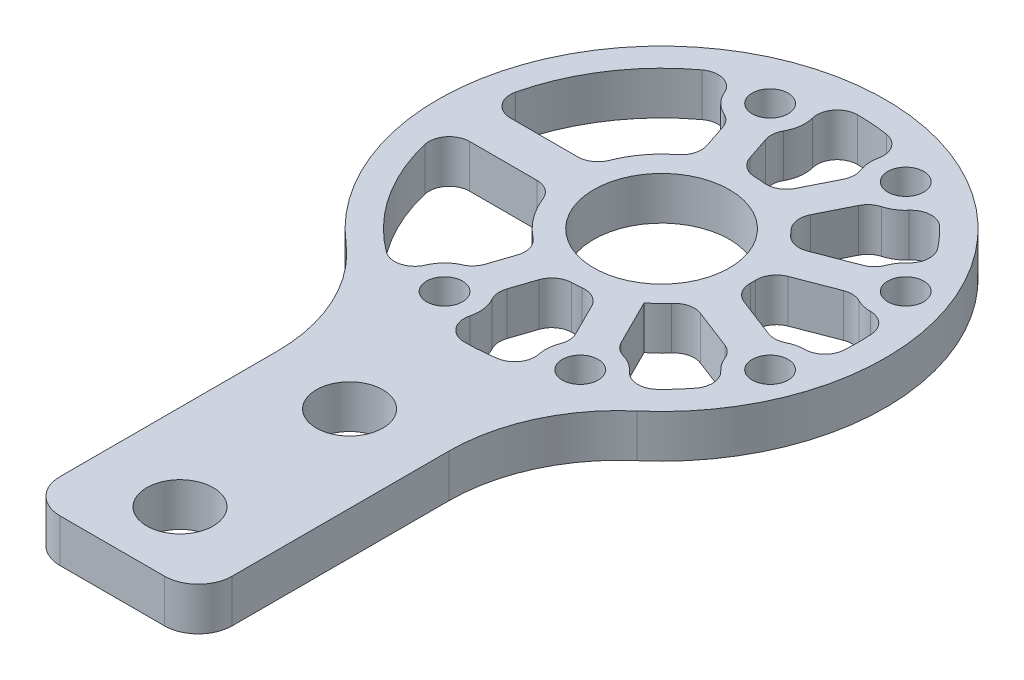
SolidWorks part; units mm, degrees
material "1060 Alloy"
ref_plane "Front Plane" through (0, 0, 0) normal (0, 0, 1) x (1, 0, 0)
ref_plane "Top Plane" through (0, 0, 0) normal (0, 1, 0) x (1, 0, 0)
ref_plane "Right Plane" through (0, 0, 0) normal (1, 0, 0) x (0, 0, -1)
sketch "Sketch1" plane through (0, 0, 0) normal (0, 1, 0) x (1, 0, 0)
  line L0 (-12.7, -81) -> (12.7, -81)
  line L1 (12.7, -81) -> (12.7, -30.4583)
  line L2 (-12.7, -81) -> (-12.7, -30.4583)
  line L3 (0, -81) -> (0, -46) construction
  arc A0 (12.7, -30.4583) -> (-12.7, -30.4583) centre (0, 0) ccw
  point P5 (0, -81)
  point P9 (0, -71)
  dimension "D2" = 66
  dimension "D1" = 25.4
  dimension "D3" = 46
  dimension "D4" = 25
  dimension "D5" = 10
extrude "Boss-Extrude1" add sketch "Sketch1" along normal blind 6.35 contours A0 L2 L0 L1
sketch "Sketch2" plane through (0, 0, 0) normal (0, -1, 0) x (1, 0, 0)
  point P14 (12, -24)
  point P16 (-8, -24)
  point P19 (2, 0)
  point P21 (26, 10)
  point P22 (26, -10)
  point P23 (-22, -10)
  point P24 (-22, 10)
  point P25 (-8, 24)
  point P26 (12, 24)
  point P27 (2, 0)
  dimension "D2" = 10
  dimension "D1" = 20
  dimension "D3" = 2
  dimension "D4" = 24
  dimension "D5" = 4
sketch "Sketch5" plane through (0, 0, 0) normal (0, -1, 0) x (1, 0, 0)
  circle A0 centre (0, 0) radius 10
  dimension "D1" = 20
extrude "Cut-Extrude1" cut sketch "Sketch5" against normal through all
hole_wizard "3/8 Clearance Hole1" positions "Sketch13" profile "Sketch14" hole size "3/8" standard "ANSI Inch" end condition through all
sketch "Sketch13" plane through (0, 0, 0) normal (0, -1, 0) x (-1, 0, 0)
  point P0 (0, -46)
  point P3 (0, -71)
sketch "Sketch14" plane through (0, 0, 46) normal (1, 0, 0) x (0, 0, -1)
  line L0 (0, 0) -> (0, 6.35)
  line L1 (0, 6.35) -> (4.9022, 6.35)
  line L2 (4.9022, 6.35) -> (4.9022, 0)
  line L5 (4.9022, 0) -> (0, 0)
  line L11 (0, -6.35) -> (0, 107.95) construction
  dimension "Thru Hole Dia." = 9.8044
  dimension "Thru Hole Depth" = 6.35
fillet "Fillet1" radius 25 2 edges at (-12.7, 3.175, 30.4583) (12.7, 3.175, 30.4583)
hole_wizard "M5 Clearance Hole1" positions "Sketch18" profile "Sketch19" hole size "M5" standard "ANSI Metric" end condition through all
sketch "Sketch18" plane through (0, 0, 0) normal (0, -1, 0) x (-1, 0, 0)
  point P0 (8, 24)
  point P3 (-12, 24)
  point P6 (-26, 10)
  point P9 (-26, -10)
  point P12 (-12, -24)
  point P15 (8, -24)
sketch "Sketch19" plane through (-8, 0, -24) normal (1, 0, 0) x (0, 0, -1)
  line L0 (0, 0) -> (0, 6.35)
  line L1 (0, 6.35) -> (2.65, 6.35)
  line L2 (2.65, 6.35) -> (2.65, 0)
  line L5 (2.65, 0) -> (0, 0)
  line L11 (0, -6.35) -> (0, 107.95) construction
  dimension "Thru Hole Dia." = 5.3
  dimension "Thru Hole Depth" = 6.35
fillet "Fillet2" radius 5 2 edges at (-12.7, 3.175, 81) (12.7, 3.175, 81)
sketch "Sketch20" plane through (0, 6.35, 0) normal (0, 1, 0) x (1, 0, 0)
  line L0 (0, 0) -> (-29, 0)
  line L1 (0, 0) -> (-8, 24)
  line L2 (0, 0) -> (12, 24)
  line L3 (0, 0) -> (26, -10)
  line L4 (0, 0) -> (26, 10)
  line L5 (0, 0) -> (12, -24)
  line L6 (0, 0) -> (-8, -24)
  line L7 (0, 2.5) -> (-29, 2.5)
  line L8 (-2.3717, 0.7906) -> (-10.3717, -23.2094)
  line L9 (-2.2361, -1.118) -> (9.7639, -25.118)
  line L10 (-0.8974, -2.3334) -> (25.1026, -12.3334)
  line L11 (0.8974, -2.3334) -> (26.8974, 7.6666)
  line L12 (2.2361, -1.118) -> (14.2361, 22.882)
  line L13 (2.3717, 0.7906) -> (-5.6283, 24.7906)
  line L14 (0, -2.5) -> (-29, -2.5)
  line L15 (2.3717, -0.7906) -> (-5.6283, -24.7906)
  line L16 (2.2361, 1.118) -> (14.2361, -22.882)
  line L17 (0.8974, 2.3334) -> (26.8974, -7.6666)
  line L18 (-0.8974, 2.3334) -> (25.1026, 12.3334)
  line L19 (-2.2361, 1.118) -> (9.7639, 25.118)
  line L20 (-2.3717, -0.7906) -> (-10.3717, 23.2094)
  line L21 (0, 3) -> (-29, 3)
  line L22 (0, -3) -> (-29, -3)
  circle A0 centre (0, 0) radius 29
  arc A1 (21.45, -25.0778) -> (-21.45, -25.0778) centre (0, 0) ccw construction
  circle A2 centre (0, 0) radius 13.5
  circle A3 centre (0, 0) radius 10 construction
  circle A4 centre (-8, 24) radius 5.15
  circle A5 centre (12, 24) radius 5.15
  circle A6 centre (26, 10) radius 5.15
  circle A7 centre (26, -10) radius 5.15
  circle A8 centre (12, -24) radius 5.15
  circle A9 centre (-8, -24) radius 5.15
  circle A10 centre (-8, 24) radius 2.65 construction
  dimension "D1" = 4
  dimension "D6" = 3.5
  dimension "D7" = 2.5
  dimension "D2" = 2.5
  dimension "D3" = 2.5
  dimension "D4" = 3
  dimension "D5" = 3
extrude "Cut-Extrude2" cut sketch "Sketch20" against normal blind 10 contours A4 A0 L21 A2 L20 | A9 L8 A2 L22 A0 | A9 A0 A8 L9 A2 L15 | A8 A0 A7 L10 A2 L16 | A7 A0 A6 L11 A2 L17 | A6 A0 A5 L12 A2 L18 | A5 A0 A4 L13 A2 L19 region at (-17.6188, 6.35, -12.2497) region at (-17.6188, 6.35, 12.2497) region at (1.6364, 6.35, -21.7099) region at (16.1994, 6.35, -14.5823) region at (1.6364, 6.35, 21.7099) region at (16.1994, 6.35, 14.5823) region at (21.8303, 6.35, 0)
fillet "Fillet3" radius 3 39 edges at (-28.8444, 3.175, -3) (-13.1624, 3.175, -3) (-6.5669, 3.175, -11.7951) (-8.9479, 3.175, -18.938) (-12.7192, 3.175, -26.0619) (-5.4617, 3.175, -28.481) (-4.2045, 3.175, -20.5191) (8.4585, 3.175, -27.739) (7.7504, 3.175, -21.0909) (-1.8235, 3.175, -13.3763) (3.6969, 3.175, -12.984) (11.4848, 3.175, -7.0958) (8.169, 3.175, -10.7479) (20.9002, 3.175, -10.7171) (24.8126, 3.175, -15.0112) (12.2225, 3.175, -18.8548) (17.1161, 3.175, -23.4102) (13.2797, 3.175, 2.429) (13.2797, 3.175, -2.429) (22.6951, 3.175, 6.0503) (28.4766, 3.175, 5.4846) (28.4766, 3.175, -5.4846) (22.6951, 3.175, -6.0503) (24.8126, 3.175, 15.0112) (20.9002, 3.175, 10.7171) (11.4848, 3.175, 7.0958) (-6.5669, 3.175, 11.7951) (-28.8444, 3.175, 3) (-13.1624, 3.175, 3) (3.6969, 3.175, 12.984) (-1.8235, 3.175, 13.3763) (17.1161, 3.175, 23.4102) (12.2225, 3.175, 18.8548) (7.7504, 3.175, 21.0909) (8.4585, 3.175, 27.739) (-12.7192, 3.175, 26.0619) (-8.9479, 3.175, 18.938) (-4.2045, 3.175, 20.5191) (-5.4617, 3.175, 28.481)
